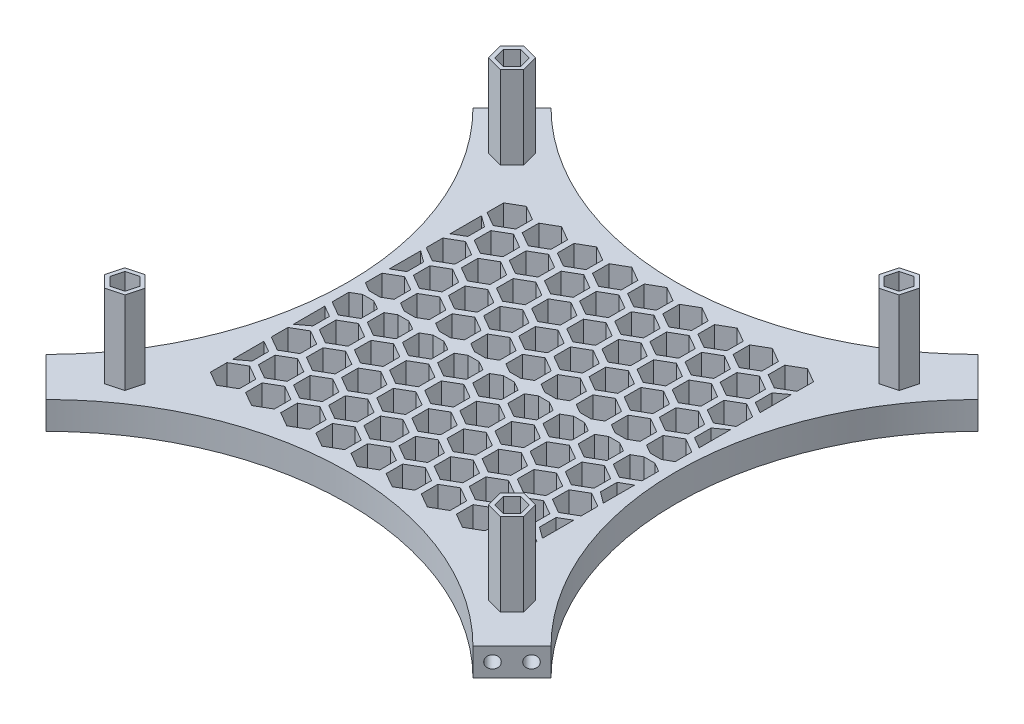
SolidWorks part; units mm, degrees
material "PLA"
ref_plane "Front Plane" through (0, 0, 0) normal (0, 0, 1) x (1, 0, 0)
ref_plane "Top Plane" through (0, 0, 0) normal (0, 1, 0) x (1, 0, 0)
ref_plane "Right Plane" through (0, 0, 0) normal (1, 0, 0) x (0, 0, -1)
sketch "Sketch1" plane through (0, 0, 0) normal (0, 1, 0) x (1, 0, 0)
  line L0 (0, 0) -> (14.1421, 14.1421)
  line L1 (168.8579, 14.1421) -> (183, 0)
  line L2 (14.1421, -168.8579) -> (0, -154.7157)
  line L3 (168.8579, -168.8579) -> (183, -154.7157)
  line L5 (14.1421, 14.1421) -> (14.1421, -168.8579) construction
  line L6 (0, 0) -> (183, 0) construction
  arc A0 (14.1421, 14.1421) -> (168.8579, 14.1421) centre (91.5, 91.5) ccw
  arc A1 (183, -154.7157) -> (183, 0) centre (260.3579, -77.3579) cw
  arc A2 (168.8579, -168.8579) -> (14.1421, -168.8579) centre (91.5, -246.2157) ccw
  arc A3 (0, -154.7157) -> (0, 0) centre (-77.3579, -77.3579) ccw
  dimension "D1" = 183
  dimension "D2" = 20
extrude "Boss-Extrude1" add sketch "Sketch1" along normal blind 10
sketch "Sketch9" plane through (0, 10, 0) normal (0, 1, 0) x (1, 0, 0)
  line L0 (7.0711, -161.7868) -> (35.3553, -133.5025) construction
  line L1 (35.3553, -21.2132) -> (147.6447, -21.2132) construction
  line L2 (35.3553, -21.2132) -> (35.3553, -133.5025) construction
  line L3 (35.3553, -133.5025) -> (147.6447, -133.5025) construction
  line L4 (147.6447, -21.2132) -> (147.6447, -133.5025) construction
  line L5 (0, -154.7157) -> (14.1421, -168.8579) construction
  line L6 (38.4435, -118.9075) -> (45.7161, -123.1064) construction
  line L7 (40.5667, -133.5025) -> (45.7781, -130.4937)
  line L8 (45.7781, -130.4937) -> (45.7781, -124.4762)
  line L9 (45.7781, -124.4762) -> (40.5667, -121.4674)
  line L10 (40.5667, -121.4674) -> (35.3553, -124.4762)
  line L11 (35.3553, -124.4762) -> (35.3553, -130.4937)
  line L12 (35.3553, -130.4937) -> (40.5667, -133.5025)
  line L13 (43.1724, -122.9718) -> (44.3277, -120.9708) construction
  line L14 (35.3553, -133.5025) -> (35.3553, -130.4937) construction
  line L15 (41.722, -113.4488) -> (46.9334, -110.44)
  line L16 (46.9334, -110.44) -> (52.1447, -113.4488)
  line L17 (52.1447, -113.4488) -> (52.1447, -119.4664)
  line L18 (52.1447, -119.4664) -> (46.9334, -122.4751)
  line L19 (46.9334, -122.4751) -> (41.722, -119.4664)
  line L20 (41.722, -119.4664) -> (41.722, -113.4488)
  line L21 (32.0427, -77.3579) -> (150.9573, -77.3579) construction
  line L22 (147.6447, -89.0523) -> (147.6447, -100.4204)
  line L23 (54.4553, -113.4488) -> (59.6667, -110.44)
  line L24 (59.6667, -110.44) -> (64.8781, -113.4488)
  line L25 (64.8781, -113.4488) -> (64.8781, -119.4664)
  line L26 (54.4553, -119.4664) -> (54.4553, -113.4488)
  line L27 (59.6667, -122.4751) -> (54.4553, -119.4664)
  line L28 (64.8781, -119.4664) -> (59.6667, -122.4751)
  line L29 (58.5114, -124.4762) -> (53.3, -121.4674)
  line L30 (53.3, -121.4674) -> (48.0887, -124.4762)
  line L31 (48.0887, -124.4762) -> (48.0887, -130.4937)
  line L32 (48.0887, -130.4937) -> (53.3, -133.5025)
  line L33 (53.3, -133.5025) -> (58.5114, -130.4937)
  line L34 (58.5114, -130.4937) -> (58.5114, -124.4762)
  line L35 (67.1886, -113.4488) -> (72.4, -110.44)
  line L36 (72.4, -110.44) -> (77.6114, -113.4488)
  line L37 (77.6114, -113.4488) -> (77.6114, -119.4664)
  line L38 (67.1886, -119.4664) -> (67.1886, -113.4488)
  line L39 (72.4, -122.4751) -> (67.1886, -119.4664)
  line L40 (77.6114, -119.4664) -> (72.4, -122.4751)
  line L41 (71.2447, -124.4762) -> (66.0334, -121.4674)
  line L42 (66.0334, -121.4674) -> (60.822, -124.4762)
  line L43 (60.822, -124.4762) -> (60.822, -130.4937)
  line L44 (60.822, -130.4937) -> (66.0334, -133.5025)
  line L45 (66.0334, -133.5025) -> (71.2447, -130.4937)
  line L46 (71.2447, -130.4937) -> (71.2447, -124.4762)
  line L47 (79.922, -113.4488) -> (85.1333, -110.44)
  line L48 (85.1333, -110.44) -> (90.3447, -113.4488)
  line L49 (90.3447, -113.4488) -> (90.3447, -119.4664)
  line L50 (79.922, -119.4664) -> (79.922, -113.4488)
  line L51 (85.1333, -122.4751) -> (79.922, -119.4664)
  line L52 (90.3447, -119.4664) -> (85.1333, -122.4751)
  line L53 (83.978, -124.4762) -> (78.7667, -121.4674)
  line L54 (78.7667, -121.4674) -> (73.5553, -124.4762)
  line L55 (73.5553, -124.4762) -> (73.5553, -130.4937)
  line L56 (73.5553, -130.4937) -> (78.7667, -133.5025)
  line L57 (78.7667, -133.5025) -> (83.978, -130.4937)
  line L58 (83.978, -130.4937) -> (83.978, -124.4762)
  line L59 (92.6553, -113.4488) -> (97.8667, -110.44)
  line L60 (97.8667, -110.44) -> (103.078, -113.4488)
  line L61 (103.078, -113.4488) -> (103.078, -119.4664)
  line L62 (92.6553, -119.4664) -> (92.6553, -113.4488)
  line L63 (97.8667, -122.4751) -> (92.6553, -119.4664)
  line L64 (103.078, -119.4664) -> (97.8667, -122.4751)
  line L65 (96.7114, -124.4762) -> (91.5, -121.4674)
  line L66 (91.5, -121.4674) -> (86.2886, -124.4762)
  line L67 (86.2886, -124.4762) -> (86.2886, -130.4937)
  line L68 (86.2886, -130.4937) -> (91.5, -133.5025)
  line L69 (91.5, -133.5025) -> (96.7114, -130.4937)
  line L70 (96.7114, -130.4937) -> (96.7114, -124.4762)
  line L71 (105.3886, -113.4488) -> (110.6, -110.44)
  line L72 (110.6, -110.44) -> (115.8114, -113.4488)
  line L73 (115.8114, -113.4488) -> (115.8114, -119.4664)
  line L74 (105.3886, -119.4664) -> (105.3886, -113.4488)
  line L75 (110.6, -122.4751) -> (105.3886, -119.4664)
  line L76 (115.8114, -119.4664) -> (110.6, -122.4751)
  line L77 (109.4447, -124.4762) -> (104.2333, -121.4674)
  line L78 (104.2333, -121.4674) -> (99.022, -124.4762)
  line L79 (99.022, -124.4762) -> (99.022, -130.4937)
  line L80 (99.022, -130.4937) -> (104.2333, -133.5025)
  line L81 (104.2333, -133.5025) -> (109.4447, -130.4937)
  line L82 (109.4447, -130.4937) -> (109.4447, -124.4762)
  line L83 (118.1219, -113.4488) -> (123.3333, -110.44)
  line L84 (123.3333, -110.44) -> (128.5447, -113.4488)
  line L85 (128.5447, -113.4488) -> (128.5447, -119.4664)
  line L86 (118.1219, -119.4664) -> (118.1219, -113.4488)
  line L87 (123.3333, -122.4751) -> (118.1219, -119.4664)
  line L88 (128.5447, -119.4664) -> (123.3333, -122.4751)
  line L89 (122.178, -124.4762) -> (116.9666, -121.4674)
  line L90 (116.9666, -121.4674) -> (111.7553, -124.4762)
  line L91 (111.7553, -124.4762) -> (111.7553, -130.4937)
  line L92 (111.7553, -130.4937) -> (116.9666, -133.5025)
  line L93 (116.9666, -133.5025) -> (122.178, -130.4937)
  line L94 (122.178, -130.4937) -> (122.178, -124.4762)
  line L95 (130.8553, -113.4488) -> (136.0666, -110.44)
  line L96 (136.0666, -110.44) -> (141.278, -113.4488)
  line L97 (141.278, -113.4488) -> (141.278, -119.4664)
  line L98 (130.8553, -119.4664) -> (130.8553, -113.4488)
  line L99 (136.0666, -122.4751) -> (130.8553, -119.4664)
  line L100 (141.278, -119.4664) -> (136.0666, -122.4751)
  line L101 (134.9113, -124.4762) -> (129.7, -121.4674)
  line L102 (129.7, -121.4674) -> (124.4886, -124.4762)
  line L103 (124.4886, -124.4762) -> (124.4886, -130.4937)
  line L104 (124.4886, -130.4937) -> (129.7, -133.5025)
  line L105 (129.7, -133.5025) -> (134.9113, -130.4937)
  line L106 (134.9113, -130.4937) -> (134.9113, -124.4762)
  line L107 (147.6447, -122.4751) -> (143.5886, -119.4664)
  line L108 (143.5886, -113.4488) -> (147.6447, -111.107)
  line L109 (91.5, -136.8152) -> (91.5, -17.9005) construction
  line L110 (143.5886, -119.4664) -> (143.5886, -113.4488)
  line L111 (39.4114, -119.4664) -> (39.4114, -113.4488)
  line L112 (35.3553, -122.4751) -> (39.4114, -119.4664)
  line L113 (147.6447, -124.4762) -> (142.4333, -121.4674)
  line L114 (142.4333, -121.4674) -> (137.2219, -124.4762)
  line L115 (137.2219, -124.4762) -> (137.2219, -130.4937)
  line L116 (137.2219, -130.4937) -> (142.4333, -133.5025)
  line L117 (142.4333, -133.5025) -> (147.6447, -130.4937)
  line L118 (147.6447, -130.4937) -> (147.6447, -124.4762)
  line L119 (54.4553, -91.394) -> (59.6667, -88.3852)
  line L120 (59.6667, -88.3852) -> (64.8781, -91.394)
  line L121 (64.8781, -91.394) -> (64.8781, -97.4116)
  line L122 (54.4553, -97.4116) -> (54.4553, -91.394)
  line L123 (59.6667, -100.4204) -> (54.4553, -97.4116)
  line L124 (64.8781, -97.4116) -> (59.6667, -100.4204)
  line L125 (58.5114, -102.4214) -> (53.3, -99.4126)
  line L126 (53.3, -99.4126) -> (48.0887, -102.4214)
  line L127 (48.0887, -102.4214) -> (48.0887, -108.439)
  line L128 (48.0887, -108.439) -> (53.3, -111.4478)
  line L129 (53.3, -111.4478) -> (58.5114, -108.439)
  line L130 (58.5114, -108.439) -> (58.5114, -102.4214)
  line L131 (67.1886, -91.394) -> (72.4, -88.3852)
  line L132 (72.4, -88.3852) -> (77.6114, -91.394)
  line L133 (77.6114, -91.394) -> (77.6114, -97.4116)
  line L134 (67.1886, -97.4116) -> (67.1886, -91.394)
  line L135 (72.4, -100.4204) -> (67.1886, -97.4116)
  line L136 (77.6114, -97.4116) -> (72.4, -100.4204)
  line L137 (71.2447, -102.4214) -> (66.0334, -99.4126)
  line L138 (66.0334, -99.4126) -> (60.822, -102.4214)
  line L139 (60.822, -102.4214) -> (60.822, -108.439)
  line L140 (60.822, -108.439) -> (66.0334, -111.4478)
  line L141 (66.0334, -111.4478) -> (71.2447, -108.439)
  line L142 (71.2447, -108.439) -> (71.2447, -102.4214)
  line L143 (79.922, -91.394) -> (85.1333, -88.3852)
  line L144 (85.1333, -88.3852) -> (90.3447, -91.394)
  line L145 (90.3447, -91.394) -> (90.3447, -97.4116)
  line L146 (79.922, -97.4116) -> (79.922, -91.394)
  line L147 (85.1333, -100.4204) -> (79.922, -97.4116)
  line L148 (90.3447, -97.4116) -> (85.1333, -100.4204)
  line L149 (83.978, -102.4214) -> (78.7667, -99.4126)
  line L150 (78.7667, -99.4126) -> (73.5553, -102.4214)
  line L151 (73.5553, -102.4214) -> (73.5553, -108.439)
  line L152 (73.5553, -108.439) -> (78.7667, -111.4478)
  line L153 (78.7667, -111.4478) -> (83.978, -108.439)
  line L154 (83.978, -108.439) -> (83.978, -102.4214)
  line L155 (92.6553, -91.394) -> (97.8667, -88.3852)
  line L156 (97.8667, -88.3852) -> (103.078, -91.394)
  line L157 (103.078, -91.394) -> (103.078, -97.4116)
  line L158 (92.6553, -97.4116) -> (92.6553, -91.394)
  line L159 (97.8667, -100.4204) -> (92.6553, -97.4116)
  line L160 (103.078, -97.4116) -> (97.8667, -100.4204)
  line L161 (96.7114, -102.4214) -> (91.5, -99.4126)
  line L162 (91.5, -99.4126) -> (86.2886, -102.4214)
  line L163 (86.2886, -102.4214) -> (86.2886, -108.439)
  line L164 (86.2886, -108.439) -> (91.5, -111.4478)
  line L165 (91.5, -111.4478) -> (96.7114, -108.439)
  line L166 (96.7114, -108.439) -> (96.7114, -102.4214)
  line L167 (105.3886, -91.394) -> (110.6, -88.3852)
  line L168 (110.6, -88.3852) -> (115.8114, -91.394)
  line L169 (115.8114, -91.394) -> (115.8114, -97.4116)
  line L170 (105.3886, -97.4116) -> (105.3886, -91.394)
  line L171 (110.6, -100.4204) -> (105.3886, -97.4116)
  line L172 (115.8114, -97.4116) -> (110.6, -100.4204)
  line L173 (109.4447, -102.4214) -> (104.2333, -99.4126)
  line L174 (104.2333, -99.4126) -> (99.022, -102.4214)
  line L175 (99.022, -102.4214) -> (99.022, -108.439)
  line L176 (99.022, -108.439) -> (104.2333, -111.4478)
  line L177 (104.2333, -111.4478) -> (109.4447, -108.439)
  line L178 (109.4447, -108.439) -> (109.4447, -102.4214)
  line L179 (118.1219, -91.394) -> (123.3333, -88.3852)
  line L180 (123.3333, -88.3852) -> (128.5447, -91.394)
  line L181 (128.5447, -91.394) -> (128.5447, -97.4116)
  line L182 (118.1219, -97.4116) -> (118.1219, -91.394)
  line L183 (123.3333, -100.4204) -> (118.1219, -97.4116)
  line L184 (128.5447, -97.4116) -> (123.3333, -100.4204)
  line L185 (122.178, -102.4214) -> (116.9666, -99.4126)
  line L186 (116.9666, -99.4126) -> (111.7553, -102.4214)
  line L187 (111.7553, -102.4214) -> (111.7553, -108.439)
  line L188 (111.7553, -108.439) -> (116.9666, -111.4478)
  line L189 (116.9666, -111.4478) -> (122.178, -108.439)
  line L190 (122.178, -108.439) -> (122.178, -102.4214)
  line L191 (130.8553, -91.394) -> (136.0666, -88.3852)
  line L192 (136.0666, -88.3852) -> (141.278, -91.394)
  line L193 (141.278, -91.394) -> (141.278, -97.4116)
  line L194 (130.8553, -97.4116) -> (130.8553, -91.394)
  line L195 (136.0666, -100.4204) -> (130.8553, -97.4116)
  line L196 (141.278, -97.4116) -> (136.0666, -100.4204)
  line L197 (134.9113, -102.4214) -> (129.7, -99.4126)
  line L198 (129.7, -99.4126) -> (124.4886, -102.4214)
  line L199 (124.4886, -102.4214) -> (124.4886, -108.439)
  line L200 (124.4886, -108.439) -> (129.7, -111.4478)
  line L201 (129.7, -111.4478) -> (134.9113, -108.439)
  line L202 (134.9113, -108.439) -> (134.9113, -102.4214)
  line L203 (143.5886, -97.4116) -> (147.6447, -100.4204)
  line L204 (143.5886, -91.394) -> (147.6447, -89.0523)
  line L205 (147.6447, -111.107) -> (147.6447, -122.4751)
  line L206 (143.5886, -97.4116) -> (143.5886, -91.394)
  line L207 (35.3553, -111.107) -> (35.3553, -122.4751)
  line L208 (39.4114, -113.4488) -> (35.3553, -111.107)
  line L209 (147.6447, -102.4214) -> (142.4333, -99.4126)
  line L210 (142.4333, -99.4126) -> (137.2219, -102.4214)
  line L211 (137.2219, -102.4214) -> (137.2219, -108.439)
  line L212 (137.2219, -108.439) -> (142.4333, -111.4478)
  line L213 (142.4333, -111.4478) -> (147.6447, -108.439)
  line L214 (147.6447, -108.439) -> (147.6447, -102.4214)
  line L215 (52.1447, -116.4576) -> (54.4553, -116.4576) construction
  line L216 (46.9334, -116.4576) -> (53.3, -105.4302) construction
  line L217 (40.5667, -127.485) -> (46.9334, -116.4576) construction
  line L218 (147.6447, -130.4937) -> (147.6447, -133.5025) construction
  line L219 (39.4114, -97.4116) -> (39.4114, -91.394)
  line L220 (39.4114, -97.4116) -> (35.3553, -100.4204)
  line L221 (58.5114, -80.3666) -> (53.3, -77.3579)
  line L222 (53.3, -77.3579) -> (48.0887, -80.3666)
  line L223 (48.0887, -80.3666) -> (48.0887, -86.3842)
  line L224 (48.0887, -86.3842) -> (53.3, -89.393)
  line L225 (53.3, -89.393) -> (58.5114, -86.3842)
  line L226 (58.5114, -86.3842) -> (58.5114, -80.3666)
  line L227 (35.3553, -89.0523) -> (35.3553, -100.4204)
  line L228 (39.4114, -91.394) -> (35.3553, -89.0523)
  line L229 (147.6447, -133.5025) -> (175.9289, -161.7868) construction
  line L230 (168.8579, -168.8579) -> (183, -154.7157) construction
  line L231 (7.0711, 7.0711) -> (35.3553, -21.2132) construction
  line L232 (14.1421, 14.1421) -> (0, 0) construction
  line L233 (71.2447, -80.3666) -> (66.0334, -77.3579)
  line L234 (66.0334, -77.3579) -> (60.822, -80.3666)
  line L235 (60.822, -80.3666) -> (60.822, -86.3842)
  line L236 (60.822, -86.3842) -> (66.0334, -89.393)
  line L237 (66.0334, -89.393) -> (71.2447, -86.3842)
  line L238 (71.2447, -86.3842) -> (71.2447, -80.3666)
  line L239 (147.6447, -21.2132) -> (175.9289, 7.0711) construction
  line L240 (183, 0) -> (168.8579, 14.1421) construction
  line L241 (35.3553, -77.3579) -> (32.0427, -77.3579) construction
  line L243 (91.5, -136.8152) -> (91.5, -133.5025) construction
  line L245 (83.978, -80.3666) -> (78.7667, -77.3579)
  line L246 (78.7667, -77.3579) -> (73.5553, -80.3666)
  line L247 (73.5553, -80.3666) -> (73.5553, -86.3842)
  line L248 (73.5553, -86.3842) -> (78.7667, -89.393)
  line L249 (78.7667, -89.393) -> (83.978, -86.3842)
  line L250 (83.978, -86.3842) -> (83.978, -80.3666)
  line L257 (96.7114, -80.3666) -> (91.5, -77.3579)
  line L258 (91.5, -77.3579) -> (86.2886, -80.3666)
  line L259 (86.2886, -80.3666) -> (86.2886, -86.3842)
  line L260 (86.2886, -86.3842) -> (91.5, -89.393)
  line L261 (91.5, -89.393) -> (96.7114, -86.3842)
  line L262 (96.7114, -86.3842) -> (96.7114, -80.3666)
  line L269 (109.4447, -80.3666) -> (104.2333, -77.3579)
  line L270 (104.2333, -77.3579) -> (99.022, -80.3666)
  line L271 (99.022, -80.3666) -> (99.022, -86.3842)
  line L272 (99.022, -86.3842) -> (104.2333, -89.393)
  line L273 (104.2333, -89.393) -> (109.4447, -86.3842)
  line L274 (109.4447, -86.3842) -> (109.4447, -80.3666)
  line L281 (122.178, -80.3666) -> (116.9666, -77.3579)
  line L282 (116.9666, -77.3579) -> (111.7553, -80.3666)
  line L283 (111.7553, -80.3666) -> (111.7553, -86.3842)
  line L284 (111.7553, -86.3842) -> (116.9666, -89.393)
  line L285 (116.9666, -89.393) -> (122.178, -86.3842)
  line L286 (122.178, -86.3842) -> (122.178, -80.3666)
  line L293 (134.9113, -80.3666) -> (129.7, -77.3579)
  line L294 (129.7, -77.3579) -> (124.4886, -80.3666)
  line L295 (124.4886, -80.3666) -> (124.4886, -86.3842)
  line L296 (124.4886, -86.3842) -> (129.7, -89.393)
  line L297 (129.7, -89.393) -> (134.9113, -86.3842)
  line L298 (134.9113, -86.3842) -> (134.9113, -80.3666)
  line L305 (147.6447, -80.3666) -> (142.4333, -77.3579)
  line L306 (142.4333, -77.3579) -> (137.2219, -80.3666)
  line L307 (137.2219, -80.3666) -> (137.2219, -86.3842)
  line L308 (137.2219, -86.3842) -> (142.4333, -89.393)
  line L309 (142.4333, -89.393) -> (147.6447, -86.3842)
  line L310 (147.6447, -86.3842) -> (147.6447, -80.3666)
  line L311 (41.722, -91.394) -> (46.9334, -88.3852)
  line L312 (46.9334, -88.3852) -> (52.1447, -91.394)
  line L313 (52.1447, -91.394) -> (52.1447, -97.4116)
  line L314 (41.722, -97.4116) -> (41.722, -91.394)
  line L315 (46.9334, -100.4204) -> (41.722, -97.4116)
  line L316 (52.1447, -97.4116) -> (46.9334, -100.4204)
  line L317 (45.7781, -102.4214) -> (40.5667, -99.4126)
  line L318 (40.5667, -99.4126) -> (35.3553, -102.4214)
  line L319 (35.3553, -102.4214) -> (35.3553, -108.439)
  line L320 (35.3553, -108.439) -> (40.5667, -111.4478)
  line L321 (40.5667, -111.4478) -> (45.7781, -108.439)
  line L322 (45.7781, -108.439) -> (45.7781, -102.4214)
  line L329 (45.7781, -80.3666) -> (40.5667, -77.3579)
  line L330 (40.5667, -77.3579) -> (35.3553, -80.3666)
  line L331 (35.3553, -80.3666) -> (35.3553, -86.3842)
  line L332 (35.3553, -86.3842) -> (40.5667, -89.393)
  line L333 (40.5667, -89.393) -> (45.7781, -86.3842)
  line L334 (45.7781, -86.3842) -> (45.7781, -80.3666)
  line L335 (54.4553, -69.3393) -> (59.6667, -66.3305) [skipped]
  line L336 (59.6667, -66.3305) -> (64.8781, -69.3393) [skipped]
  line L337 (67.1886, -69.3393) -> (72.4, -66.3305) [skipped]
  line L338 (72.4, -66.3305) -> (77.6114, -69.3393) [skipped]
  line L339 (79.922, -69.3393) -> (85.1333, -66.3305) [skipped]
  line L340 (85.1333, -66.3305) -> (90.3447, -69.3393) [skipped]
  line L341 (92.6553, -69.3393) -> (97.8667, -66.3305) [skipped]
  line L342 (97.8667, -66.3305) -> (103.078, -69.3393) [skipped]
  line L343 (105.3886, -69.3393) -> (110.6, -66.3305) [skipped]
  line L344 (110.6, -66.3305) -> (115.8114, -69.3393) [skipped]
  line L345 (118.1219, -69.3393) -> (123.3333, -66.3305) [skipped]
  line L346 (123.3333, -66.3305) -> (128.5447, -69.3393) [skipped]
  line L347 (130.8553, -69.3393) -> (136.0666, -66.3305) [skipped]
  line L348 (136.0666, -66.3305) -> (141.278, -69.3393) [skipped]
  line L349 (143.5886, -69.3393) -> (148.8, -66.3305) [skipped]
  line L350 (148.8, -66.3305) -> (154.0113, -69.3393) [skipped]
  line L351 (41.722, -69.3393) -> (46.9334, -66.3305) [skipped]
  line L352 (46.9334, -66.3305) -> (52.1447, -69.3393) [skipped]
  line L353 (64.8781, -69.3393) -> (64.8781, -75.3568) [skipped]
  line L354 (54.4553, -75.3568) -> (54.4553, -69.3393) [skipped]
  line L355 (77.6114, -69.3393) -> (77.6114, -75.3568) [skipped]
  line L356 (67.1886, -75.3568) -> (67.1886, -69.3393) [skipped]
  line L357 (90.3447, -69.3393) -> (90.3447, -75.3568) [skipped]
  line L358 (79.922, -75.3568) -> (79.922, -69.3393) [skipped]
  line L359 (103.078, -69.3393) -> (103.078, -75.3568) [skipped]
  line L360 (92.6553, -75.3568) -> (92.6553, -69.3393) [skipped]
  line L361 (115.8114, -69.3393) -> (115.8114, -75.3568) [skipped]
  line L362 (105.3886, -75.3568) -> (105.3886, -69.3393) [skipped]
  line L363 (128.5447, -69.3393) -> (128.5447, -75.3568) [skipped]
  line L364 (118.1219, -75.3568) -> (118.1219, -69.3393) [skipped]
  line L365 (141.278, -69.3393) -> (141.278, -75.3568) [skipped]
  line L366 (130.8553, -75.3568) -> (130.8553, -69.3393) [skipped]
  line L367 (154.0113, -69.3393) -> (154.0113, -75.3568) [skipped]
  line L368 (143.5886, -75.3568) -> (143.5886, -69.3393) [skipped]
  line L369 (52.1447, -69.3393) -> (52.1447, -75.3568) [skipped]
  line L370 (41.722, -75.3568) -> (41.722, -69.3393) [skipped]
  line L371 (148.8, -78.3656) -> (143.5886, -75.3568) [skipped]
  line L372 (154.0113, -75.3568) -> (148.8, -78.3656) [skipped]
  line L373 (141.278, -75.3568) -> (136.0666, -78.3656) [skipped]
  line L374 (136.0666, -78.3656) -> (130.8553, -75.3568) [skipped]
  line L375 (128.5447, -75.3568) -> (123.3333, -78.3656) [skipped]
  line L376 (123.3333, -78.3656) -> (118.1219, -75.3568) [skipped]
  line L377 (115.8114, -75.3568) -> (110.6, -78.3656) [skipped]
  line L378 (110.6, -78.3656) -> (105.3886, -75.3568) [skipped]
  line L379 (103.078, -75.3568) -> (97.8667, -78.3656) [skipped]
  line L380 (97.8667, -78.3656) -> (92.6553, -75.3568) [skipped]
  line L381 (90.3447, -75.3568) -> (85.1333, -78.3656) [skipped]
  line L382 (85.1333, -78.3656) -> (79.922, -75.3568) [skipped]
  line L383 (77.6114, -75.3568) -> (72.4, -78.3656) [skipped]
  line L384 (72.4, -78.3656) -> (67.1886, -75.3568) [skipped]
  line L385 (64.8781, -75.3568) -> (59.6667, -78.3656) [skipped]
  line L386 (59.6667, -78.3656) -> (54.4553, -75.3568) [skipped]
  line L387 (52.1447, -75.3568) -> (46.9334, -78.3656) [skipped]
  line L388 (46.9334, -78.3656) -> (41.722, -75.3568) [skipped]
  line L389 (143.5886, -91.394) -> (148.8, -88.3852) [skipped]
  line L390 (148.8, -88.3852) -> (154.0113, -91.394) [skipped]
  line L391 (154.0113, -91.394) -> (154.0113, -97.4116) [skipped]
  line L392 (154.0113, -97.4116) -> (148.8, -100.4204) [skipped]
  line L393 (148.8, -100.4204) -> (143.5886, -97.4116) [skipped]
  line L394 (143.5886, -113.4488) -> (148.8, -110.44) [skipped]
  line L395 (148.8, -110.44) -> (154.0113, -113.4488) [skipped]
  line L396 (154.0113, -113.4488) -> (154.0113, -119.4664) [skipped]
  line L397 (154.0113, -119.4664) -> (148.8, -122.4751) [skipped]
  line L398 (148.8, -122.4751) -> (143.5886, -119.4664) [skipped]
  circle A0 centre (40.5667, -127.485) radius 5.2114 construction
  circle A1 centre (46.9334, -116.4576) radius 5.2114 construction
  arc A2 (0, -154.7157) -> (0, 0) centre (-77.3579, -77.3579) ccw construction
  circle A4 centre (59.6667, -116.4576) radius 5.2114 construction
  circle A5 centre (53.3, -127.485) radius 5.2114 construction
  circle A6 centre (72.4, -116.4576) radius 5.2114 construction
  circle A7 centre (66.0334, -127.485) radius 5.2114 construction
  circle A8 centre (85.1333, -116.4576) radius 5.2114 construction
  circle A9 centre (78.7667, -127.485) radius 5.2114 construction
  circle A10 centre (97.8667, -116.4576) radius 5.2114 construction
  circle A11 centre (91.5, -127.485) radius 5.2114 construction
  circle A12 centre (110.6, -116.4576) radius 5.2114 construction
  circle A13 centre (104.2333, -127.485) radius 5.2114 construction
  circle A14 centre (123.3333, -116.4576) radius 5.2114 construction
  circle A15 centre (116.9666, -127.485) radius 5.2114 construction
  circle A16 centre (136.0666, -116.4576) radius 5.2114 construction
  circle A17 centre (129.7, -127.485) radius 5.2114 construction
  arc A18 (168.8579, -168.8579) -> (14.1421, -168.8579) centre (91.5, -246.2157) ccw construction
  circle A19 centre (142.4333, -127.485) radius 5.2114 construction
  circle A20 centre (59.6667, -94.4028) radius 5.2114 construction
  circle A21 centre (53.3, -105.4302) radius 5.2114 construction
  circle A22 centre (72.4, -94.4028) radius 5.2114 construction
  circle A23 centre (66.0334, -105.4302) radius 5.2114 construction
  circle A24 centre (85.1333, -94.4028) radius 5.2114 construction
  circle A25 centre (78.7667, -105.4302) radius 5.2114 construction
  circle A26 centre (97.8667, -94.4028) radius 5.2114 construction
  circle A27 centre (91.5, -105.4302) radius 5.2114 construction
  circle A28 centre (110.6, -94.4028) radius 5.2114 construction
  circle A29 centre (104.2333, -105.4302) radius 5.2114 construction
  circle A30 centre (123.3333, -94.4028) radius 5.2114 construction
  circle A31 centre (116.9666, -105.4302) radius 5.2114 construction
  circle A32 centre (136.0666, -94.4028) radius 5.2114 construction
  circle A33 centre (129.7, -105.4302) radius 5.2114 construction
  arc A34 (14.1421, 14.1421) -> (168.8579, 14.1421) centre (91.5, 91.5) ccw construction
  circle A35 centre (142.4333, -105.4302) radius 5.2114 construction
  arc A36 (183, 0) -> (183, -154.7157) centre (260.3579, -77.3579) ccw construction
  circle A37 centre (53.3, -83.3754) radius 5.2114 construction
  circle A39 centre (66.0334, -83.3754) radius 5.2114 construction
  circle A41 centre (78.7667, -83.3754) radius 5.2114 construction
  circle A43 centre (91.5, -83.3754) radius 5.2114 construction
  circle A45 centre (104.2333, -83.3754) radius 5.2114 construction
  circle A47 centre (116.9666, -83.3754) radius 5.2114 construction
  circle A49 centre (129.7, -83.3754) radius 5.2114 construction
  circle A51 centre (142.4333, -83.3754) radius 5.2114 construction
  circle A52 centre (46.9334, -94.4028) radius 5.2114 construction
  circle A53 centre (40.5667, -105.4302) radius 5.2114 construction
  circle A55 centre (40.5667, -83.3754) radius 5.2114 construction
  circle A56 centre (46.9334, -72.348) radius 5.2114 construction
  circle A57 centre (59.6667, -72.348) radius 5.2114 construction
  circle A58 centre (72.4, -72.348) radius 5.2114 construction
  circle A59 centre (85.1333, -72.348) radius 5.2114 construction
  circle A60 centre (97.8667, -72.348) radius 5.2114 construction
  circle A61 centre (110.6, -72.348) radius 5.2114 construction
  circle A62 centre (123.3333, -72.348) radius 5.2114 construction
  circle A63 centre (136.0666, -72.348) radius 5.2114 construction
  circle A64 centre (148.8, -72.348) radius 5.2114 construction
  circle A65 centre (148.8, -94.4028) radius 5.2114 construction
  circle A66 centre (148.8, -116.4576) radius 5.2114 construction
  point P7 (32.0427, -77.3579)
  point P34 (150.9573, -77.3579)
  dimension "D1" = 40
  dimension "D2" = 9
  dimension "D3" = 3
extrude "Cut-Extrude1" cut sketch "Sketch9" against normal through all
sketch "Sketch12" plane through (0, 10, 0) normal (0, 1, 0) x (1, 0, 0)
  line L0 (91.5, -17.9005) -> (91.5, -136.8152) construction
  line L1 (32.0427, -77.3579) -> (150.9573, -77.3579) construction
  arc A0 (14.1421, 14.1421) -> (168.8579, 14.1421) centre (91.5, 91.5) ccw construction
  arc A1 (168.8579, -168.8579) -> (14.1421, -168.8579) centre (91.5, -246.2157) ccw construction
  arc A2 (0, -154.7157) -> (0, 0) centre (-77.3579, -77.3579) ccw construction
  arc A3 (183, 0) -> (183, -154.7157) centre (260.3579, -77.3579) ccw construction
ref_point "Point1"
ref_plane "Plane1" through (0, 0, 77.36) normal (0, 0, 1) x (1, 0, 0)
mirror "Mirror2" about plane through (0, 0, 77.36) normal (0, 0, 1) of "Cut-Extrude1"
sketch "Sketch10" plane through (0, 10, 0) normal (0, 1, 0) x (1, 0, 0)
  line L0 (32.0366, -76.2029) -> (150.9634, -76.2029)
  line L1 (32.0366, -78.5129) -> (150.9634, -78.5129)
  line L2 (32.0427, -77.3579) -> (150.9573, -77.3579) construction
  line L3 (91.5, -76.2029) -> (91.5, -78.5129) construction
  arc A0 (0, -154.7157) -> (0, 0) centre (-77.3579, -77.3579) ccw construction
  arc A1 (183, 0) -> (183, -154.7157) centre (260.3579, -77.3579) ccw construction
  arc A2 (0, -154.7157) -> (0, 0) centre (-77.3579, -77.3579) ccw
  arc A3 (183, 0) -> (183, -154.7157) centre (260.3579, -77.3579) ccw
  point P14 (91.5, -77.3579)
  dimension "D1" = 2.31
extrude "Boss-Extrude2" add sketch "Sketch10" against normal up to surface (10 mm away) contours A3 L0 A2 L1 region at (91.5, 10, 77.3579) up to face at (46.9334, 0, 60.3172)
sketch "Sketch11" plane through (168.8579, 0, 168.8579) normal (0.7071, 0, 0.7071) x (0.7071, 0, -0.7071)
  line L0 (0, 5) -> (20, 5) construction
  line L1 (0, 10) -> (0, 0) construction
  line L2 (20, 10) -> (20, 0) construction
  line L3 (5, 7.25) -> (15, 7.25)
  line L4 (10, 7.25) -> (10, 5) construction
  line L5 (5, 2.75) -> (10, 2.75) construction
  line L6 (10, 2.75) -> (10, 5) construction
  line L7 (5, 2.75) -> (0, 2.75) construction
  circle A0 centre (5, 5) radius 2.25
  circle A1 centre (15, 5) radius 2.25
  dimension "D1" = 4.5
extrude "Cut-Extrude2" cut sketch "Sketch11" against normal blind 15 contours A0 | A1 region at (179.4645, 5, 158.2513) region at (172.3934, 5, 165.3223)
ref_plane "Plane2" through (91.5, 0, 0) normal (1, 0, 0) x (0, 0, -1)
ref_plane "Plane3" through (0, 0, 77.3579) normal (0, 0, 1) x (1, 0, 0)
ref_axis "Axis1" through (91.5, -0.5, 77.3579) along (0, 1, 0)
pattern_circular "CirPattern1" count 4 over 360 about axis through (91.5, -0.5, 77.3579) along (0, 1, 0) of "Cut-Extrude2" reverse direction yes
sketch "Sketch13" plane through (0, 10, 0) normal (0, 1, 0) x (1, 0, 0)
  line L0 (0, -154.7157) -> (14.1421, -168.8579) construction
  line L1 (27.1752, -145.9377) -> (22.9201, -141.6827)
  line L2 (22.9201, -141.6827) -> (17.1076, -143.2401)
  line L3 (17.1076, -143.2401) -> (15.5501, -149.0527)
  line L4 (15.5501, -149.0527) -> (19.8052, -153.3077)
  line L5 (19.8052, -153.3077) -> (25.6177, -151.7503)
  line L6 (25.6177, -151.7503) -> (27.1752, -145.9377)
  line L7 (7.0711, -161.7868) -> (175.9289, 7.0711) construction
  line L8 (183, 0) -> (168.8579, 14.1421) construction
  line L9 (35.3553, -127.485) -> (45.7781, -127.485) construction
  line L10 (35.3553, -124.4762) -> (35.3553, -130.4937) construction
  line L11 (45.7781, -130.4937) -> (45.7781, -124.4762) construction
  line L12 (16.3289, -146.1464) -> (26.3965, -148.844) construction
  line L13 (25.6137, -146.3561) -> (22.5017, -143.2442)
  line L14 (22.5017, -143.2442) -> (18.2507, -144.3832)
  line L15 (18.2507, -144.3832) -> (17.1116, -148.6343)
  line L16 (17.1116, -148.6343) -> (20.2236, -151.7462)
  line L17 (20.2236, -151.7462) -> (24.4746, -150.6072)
  line L18 (24.4746, -150.6072) -> (25.6137, -146.3561)
  line L19 (16.6912, -144.7941) -> (26.7588, -147.4917) construction
  circle A0 centre (21.3627, -147.4952) radius 5.2114 construction
  circle A1 centre (21.3627, -147.4952) radius 3.8114
  dimension "D1" = 15
  dimension "D2" = 1.4
extrude "Boss-Extrude3" add sketch "Sketch13" along normal blind 30 contours L5 L6 L1 L2 L3 L4 L18 L17 L16 L15 L14 L13 region at (26.2377, 10, 148.8015)
pattern_circular "CirPattern2" count 4 over 360 about axis through (91.5, -0.5, 77.3579) along (0, 1, 0) of "Boss-Extrude3"
